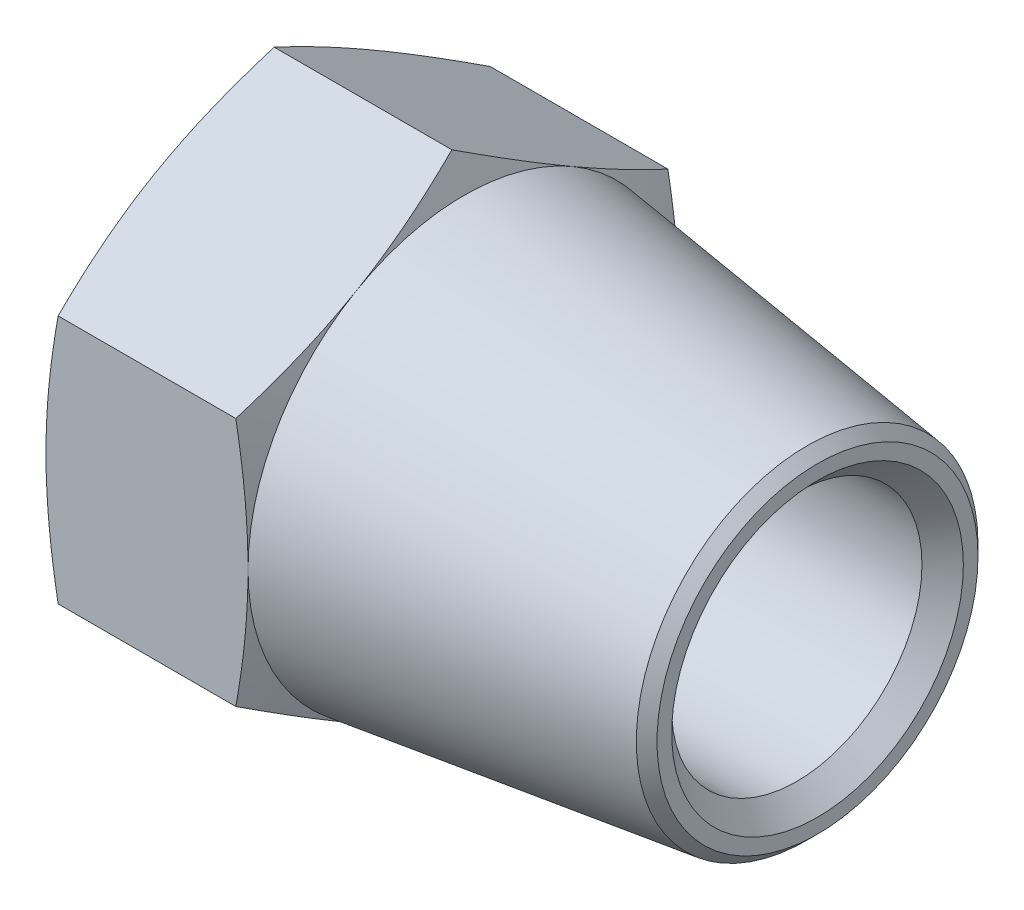
SolidWorks part; units mm, degrees
material "Brass"
ref_plane "Front" through (0, 0, 0) normal (0, 0, 1) x (1, 0, 0)
ref_plane "Top" through (0, 0, 0) normal (0, 1, 0) x (1, 0, 0)
ref_plane "Right" through (0, 0, 0) normal (1, 0, 0) x (0, 0, -1)
sketch "Sketch1" plane through (0, 0, 0) normal (0, 0, 1) x (1, 0, 0)
  line L1 (0, 0) -> (28.575, 0) construction
  line L2 (0, 0) -> (9.525, 0)
  line L3 (0, 0) -> (0, 9.525)
  line L4 (0, 9.525) -> (9.525, 9.525)
  line L5 (9.525, 0) -> (9.525, 9.525)
  line L12 (0, 0) -> (-2.0444, 0) construction
  dimension "Thread Dia" = 19.05
  dimension "D1" = 9.525
  dimension "L" = 28.575
revolve "Revolve1" add sketch "Sketch1" angle 360 about L12
sketch "Sketch12" plane through (0, 0, 0) normal (-1, 0, 0) x (0, 0, 1)
  circle A1 centre (0, 0) radius 9.525
  circle A2 centre (0, 0) radius 9.525
  dimension "D1" = 0
curve "Helix/Spiral1" pitch 1.5875 height 11.1125 turns 7 parameters "Pitch"=1.5875
sketch "Sketch13" plane through (0, 0, 0) normal (0, 0, 1) x (1, 0, 0)
  line L0 (-1.3891, 9.525) -> (0, 9.525)
  line L1 (0, 9.525) -> (-0.5953, 8.4939)
  line L2 (-0.5953, 8.4939) -> (-0.7938, 8.4939)
  line L3 (-0.7938, 8.4939) -> (-1.3891, 9.525)
  line L4 (-0.6945, 8.4939) -> (-0.6945, 9.525) construction
  line L5 (-1.0914, 9.0094) -> (-0.2977, 9.0094) construction
  dimension "D1" = 60
  dimension "D2" = 0.1984
  dimension "D3" = 0.7937
sweep "Cut-Sweep1" cut profiles "Sketch13" path "Helix/Spiral1" align with end faces yes
sketch "Sketch4" plane through (0, 0, 0) normal (-1, 0, 0) x (0, 0, 1)
  line L1 (0, 12.8316) -> (-11.1125, 6.4158)
  line L2 (-11.1125, 6.4158) -> (-11.1125, -6.4158)
  line L3 (-11.1125, -6.4158) -> (0, -12.8316)
  line L4 (0, -12.8316) -> (11.1125, -6.4158)
  line L5 (11.1125, -6.4158) -> (11.1125, 6.4158)
  line L6 (11.1125, 6.4158) -> (0, 12.8316)
  circle A0 centre (0, 0) radius 11.1125 construction
  dimension "Hex" = 22.225
extrude "Extrude1" add sketch "Sketch4" against normal blind 10.3909 separate body
combine bodies "Combine1" operation type subtract main body 150 bodies to subtract 159
sketch "Sketch9" plane through (0, 0, 0) normal (-1, 0, 0) x (0, 0, 1)
  circle A0 centre (0, 0) radius 9.525
extrude "Cut-Extrude1" cut sketch "Sketch9" against normal through all draft 45
sketch "Sketch10" plane through (0, 0, 0) normal (-1, 0, 0) x (0, 0, 1)
  circle A0 centre (0, 0) radius 11.1125 construction
  circle A1 centre (0, 0) radius 11.1125
extrude "Cut-Extrude2" cut sketch "Sketch10" against normal through all draft 70 flip side to cut
sketch "Sketch11" plane through (10.3909, 0, 0) normal (1, 0, 0) x (0, 0, -1)
  circle A0 centre (0, 0) radius 11.1125 construction
  circle A1 centre (0, 0) radius 11.1125
extrude "Cut-Extrude3" cut sketch "Sketch11" against normal through all draft 70 flip side to cut
sketch "Sketch5" plane through (0, 0, 0) normal (0, 0, 1) x (1, 0, 0)
  line L0 (10.3909, 11.1125) -> (10.3909, 6.4389)
  line L1 (10.3909, 12.8316) -> (10.3909, 6.4158) construction
  line L2 (10.3909, 6.4389) -> (27.5104, 6.4389)
  line L3 (27.5104, 6.4389) -> (28.575, 7.5035)
  line L4 (28.575, 7.5035) -> (28.575, 8.2563)
  line L5 (28.575, 8.2563) -> (28.0427, 8.7886)
  line L6 (28.0427, 8.7886) -> (10.3909, 11.1125)
  line L7 (0, 11.1125) -> (10.3909, 11.1125) construction
  line L8 (0, 11.1125) -> (0, -11.1125) construction
  line L9 (0, 6.4158) -> (0, 12.8316) construction
  line L11 (28.575, 0) -> (0, 0) construction
  point P5 (28.0427, 6.9712)
  dimension "D1" = 45
  dimension "D" = 12.8778
  dimension "D2" = 7.5
revolve "Revolve2" add sketch "Sketch5" angle 360 about L11
sketch "Sketch7" plane through (0, 0, 0) normal (0, 0, 1) x (1, 0, 0)
  line L0 (19.05, 0) -> (9.525, 9.525)
  line L1 (9.525, 9.525) -> (9.525, 0)
  line L2 (9.525, 0) -> (19.05, 0)
  line L3 (0, 0) -> (28.575, 0) construction
  dimension "D1" = 45
revolve "Cut-Revolve3" cut sketch "Sketch7" angle 360 about L1
equation "\"D1@Sketch1\" = \"L@Sketch1\"/3"
equation "\"D1@Extrude1\" = \"L@Sketch1\"/2.75"
equation "\"D3@Helix/Spiral1\" = \"D1@Sketch1\"+\"Pitch@Helix/Spiral1\""
equation "\"D2@Sketch13\" = \"Pitch@Helix/Spiral1\"*.125"
equation "\"D3@Sketch13\" = \"Pitch@Helix/Spiral1\"*.50"
